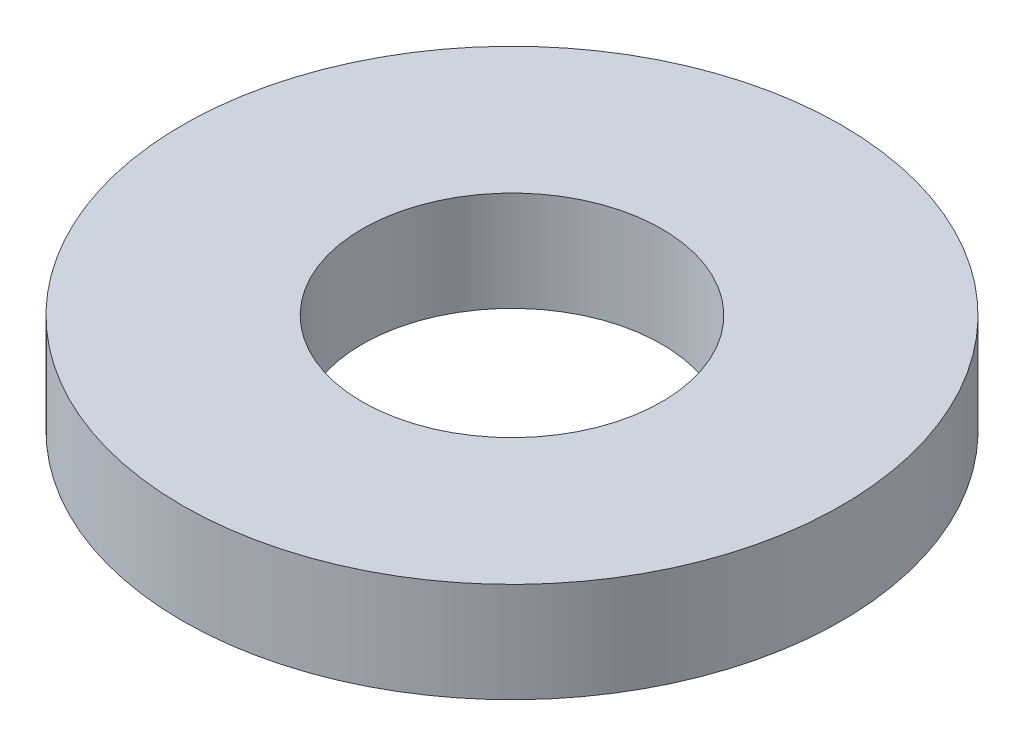
SolidWorks part; units mm, degrees
ref_plane "Front Plane" through (0, 0, 0) normal (0, 0, 1) x (1, 0, 0)
ref_plane "Top Plane" through (0, 0, 0) normal (0, 1, 0) x (1, 0, 0)
ref_plane "Right Plane" through (0, 0, 0) normal (1, 0, 0) x (0, 0, -1)
sketch "Sketch1" plane through (0, 0, 0) normal (0, 1, 0) x (1, 0, 0)
  circle A0 centre (0, 0) radius 82.5
  dimension "FLANGE_OD" = 165
extrude "Boss-Extrude1" add sketch "Sketch1" along normal blind 25
sketch "Sketch2" plane through (0, 0, 0) normal (0, 1, 0) x (1, 0, 0)
  circle A0 centre (0, 0) radius 37.5
  dimension "BORE_D" = 75
extrude "Cut-Extrude1" cut sketch "Sketch2" along normal through all
sketch "Sketch3" plane through (0, 25, 0) normal (0, 1, 0) x (1, 0, 0)
  circle A0 centre (0, 0) radius 26.834 construction
  circle A1 centre (-26.834, 0) radius 7.8162
  dimension "BOLT_D" = 15.6324
  dimension "BOLT_PCD" = 53.668
extrude "Cut-Extrude2" cut sketch "Sketch3" against normal blind 22.9457 rebuild error yes
pattern_circular "CirPattern1" count 4 over 360 rebuild error yes
